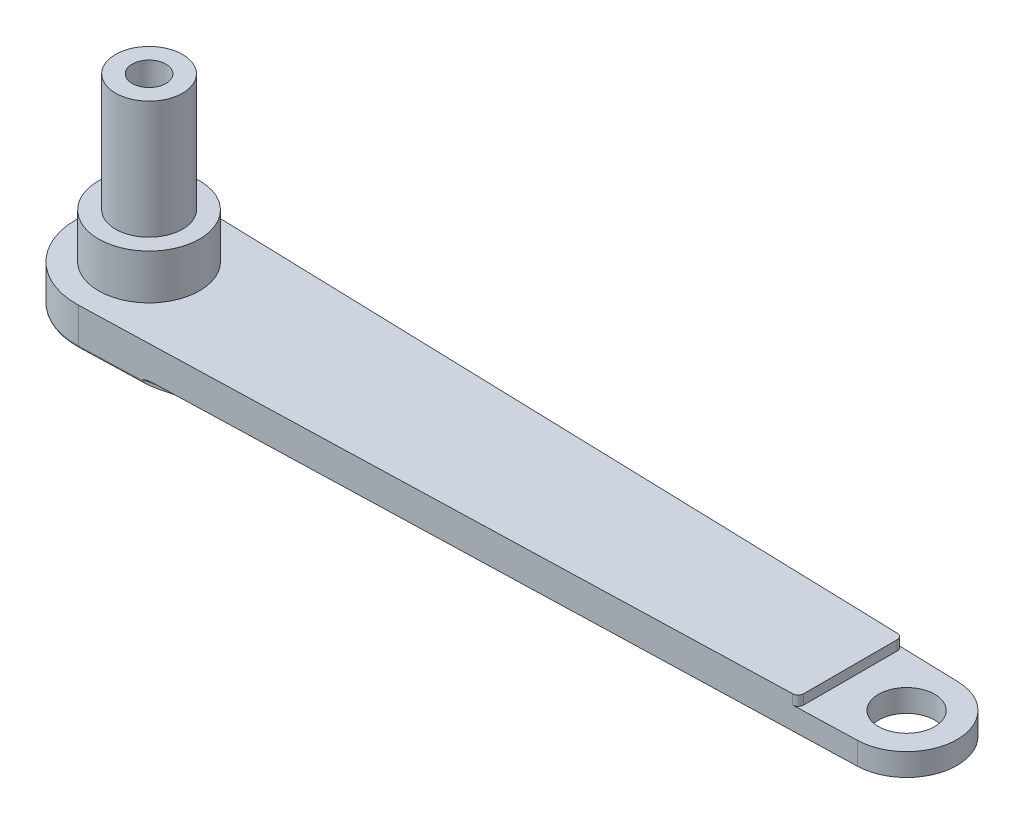
SolidWorks part; units mm, degrees
ref_plane "Front Plane" through (0, 0, 0) normal (0, 0, 1) x (1, 0, 0)
ref_plane "Top Plane" through (0, 0, 0) normal (0, 1, 0) x (1, 0, 0)
ref_plane "Right Plane" through (0, 0, 0) normal (1, 0, 0) x (0, 0, -1)
sketch "Sketch2" plane through (0, 0, 0) normal (0, 1, 0) x (1, 0, 0)
  line L0 (-36.9106, 0) -> (120.0894, 0) construction
  line L1 (-23.5254, 12.9943) -> (111.3561, 8.996)
  line L2 (-23.5254, -12.9943) -> (111.3561, -8.996)
  circle A0 centre (111.0894, 0) radius 5
  arc A1 (111.3561, -8.996) -> (111.3561, 8.996) centre (111.0894, 0) ccw
  arc A2 (-23.5254, 12.9943) -> (-23.5254, -12.9943) centre (-23.9106, 0) ccw
  dimension "D1" = 18
  dimension "D2" = 10
  dimension "D3" = 26
  dimension "D4" = 135
extrude "Boss-Extrude1" add sketch "Sketch2" along normal blind 6.75
sketch "Sketch3" plane through (0, 6.75, 0) normal (0, 1, 0) x (1, 0, 0)
  circle A0 centre (-23.9106, 0) radius 6
sketch "Sketch4" plane through (0, 6.75, 0) normal (0, 1, 0) x (1, 0, 0)
  circle A0 centre (-23.9106, 0) radius 5.975
  dimension "D1" = 11.95
extrude "Boss-Extrude3" add sketch "Sketch4" along normal blind 29 contours A0
sketch "Sketch6" plane through (0, 6.75, 0) normal (0, 1, 0) x (1, 0, 0)
  line L0 (101.0894, 0) -> (101.0894, 15.9577)
  line L1 (101.0894, 15.9577) -> (123.6962, 15.9577)
  line L2 (123.6962, 15.9577) -> (123.6962, -15.6622)
  line L3 (123.6962, -15.6622) -> (101.0894, -15.6622)
  line L4 (101.0894, -15.6622) -> (101.0894, 0)
  circle A0 centre (111.0894, 0) radius 5 construction
  dimension "D1" = 10
extrude "Cut-Extrude2" cut sketch "Sketch6" against normal blind 1.75
fillet "Fillet1" radius 1 2 edges at (101.0894, 5.875, -9.3004) (101.0894, 5.875, 9.3004)
sketch "Sketch7" plane through (0, 6.75, 0) normal (0, 1, 0) x (1, 0, 0)
  circle A0 centre (-23.9106, 0) radius 9
  dimension "D1" = 18
extrude "Boss-Extrude4" add sketch "Sketch7" along normal blind 8
sketch "Sketch5" plane through (0, 0, 0) normal (0, -1, 0) x (1, 0, 0)
  circle A0 centre (-23.9106, 0) radius 3
  dimension "D1" = 6
extrude "Cut-Extrude1" cut sketch "Sketch5" against normal through all
sketch "Sketch8" plane through (0, 0, 0) normal (0, -1, 0) x (1, 0, 0)
  line L0 (-30.5356, 0) -> (10.4644, 0)
  line L3 (-23.9106, 6.625) -> (6.5466, 4.237)
  line L4 (-23.9106, -6.625) -> (6.5466, -4.237)
  arc A0 (-23.9106, 6.625) -> (-23.9106, -6.625) centre (-23.9106, 0) ccw
  arc A2 (6.5466, -4.237) -> (6.5466, 4.237) centre (6.2144, 0) ccw
  circle M5 centre (-23.9106, 0) radius 3
  dimension "D1" = 13.25
  dimension "D3" = 4.25
  dimension "D2" = 41
extrude "Cut-Extrude3" cut sketch "Sketch8" against normal blind 5 contours A0 L0 M5 | L0 A0 M5 region at (-10.5736, 0, 2.8104) region at (-10.5736, 0, -2.8104)
sketch "Sketch9" plane through (0, 0, 0) normal (0, -1, 0) x (1, 0, 0)
  line L0 (-23.5254, 12.9943) -> (111.3561, 8.996) construction
  line L1 (-12.4521, 12.6661) -> (77.5479, 9.9982)
  line L2 (77.5479, -9.9982) -> (-12.4521, 12.6661)
  line L3 (111.3561, -8.996) -> (-23.5254, -12.9943) construction
  arc A0 (77.5479, -9.9982) -> (77.5479, 9.9982) centre (111.0894, 0) ccw
  dimension "D1" = 70
  dimension "D2" = 90
extrude "Cut-Extrude4" cut sketch "Sketch9" against normal blind 1
sketch "Sketch10" plane through (0, 5, 0) normal (0, -1, 0) x (1, 0, 0)
  line L0 (-8.682, 5.431) -> (6.5466, 4.237)
  line L1 (-23.9106, 6.625) -> (6.5466, 4.237) construction
  line L2 (-8.682, -5.431) -> (6.5466, -4.237)
  line L3 (-23.9106, -6.625) -> (6.5466, -4.237) construction
  line L4 (-8.682, 5.431) -> (-13.6667, 5.8218)
  line L5 (-23.9106, 6.625) -> (6.5466, 4.237) construction
  line L6 (-13.6667, 5.8218) -> (-13.6667, -5.8218)
  line L7 (-23.9106, -6.625) -> (6.5466, -4.237) construction
  line L8 (-13.6667, -5.8218) -> (-8.682, -5.431)
  arc A0 (6.5466, 4.237) -> (6.5466, -4.237) centre (6.2144, 0) cw
  dimension "D1" = 5
extrude "Boss-Extrude5" add sketch "Sketch10" along normal blind 0.5
sketch "Sketch11" plane through (0, 5, 0) normal (0, -1, 0) x (1, 0, 0)
  circle A0 centre (-23.9106, 0) radius 3
  circle A1 centre (-23.9106, 0) radius 1.75
  dimension "D1" = 3.5
extrude "Boss-Extrude6" add sketch "Sketch11" against normal blind 1.75
fillet "Fillet2" radius 0.5 1 edges at (32.5479, 1, 1.3339)
fillet "Fillet3" radius 0.5 3 edges at (-17.9888, 0, 12.8302) (-36.9106, 0, 0) (27.0112, 0, -11.4963)
